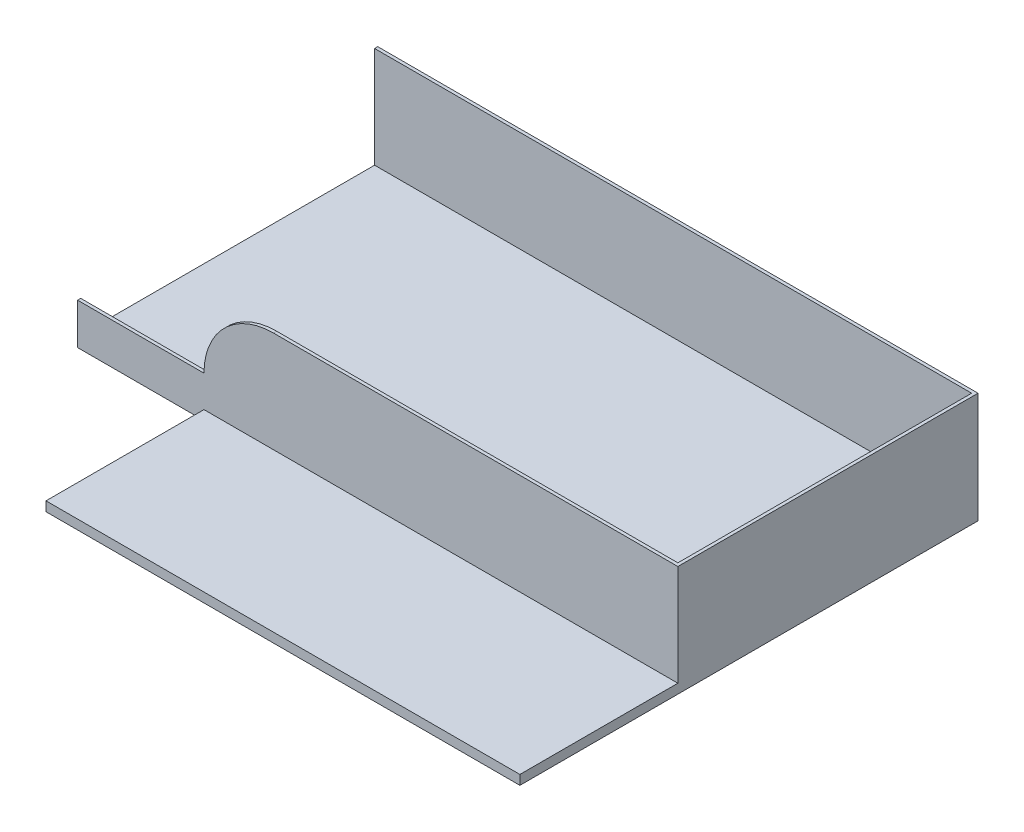
SolidWorks part; units mm, degrees
ref_plane "Front Plane" through (0, 0, 0) normal (0, 0, 1) x (1, 0, 0)
ref_plane "Top Plane" through (0, 0, 0) normal (0, 1, 0) x (1, 0, 0)
ref_plane "Right Plane" through (0, 0, 0) normal (1, 0, 0) x (0, 0, -1)
sketch "Sketch1" plane through (0, 0, 0) normal (0, 1, 0) x (1, 0, 0)
  line L0 (0, -10) -> (1890, -10)
  line L1 (0, 0) -> (1900, 0)
  line L2 (0, 0) -> (0, -950)
  line L3 (0, -950) -> (1900, -950)
  line L4 (1900, 0) -> (1900, -950)
  line L5 (1890, -10) -> (1890, -950)
  line L8 (400, -1450) -> (400, -950)
  line L9 (1900, -950) -> (0, -950)
  line L10 (1900, -950) -> (1900, -1450)
  line L11 (1900, -1450) -> (400, -1450)
  line L12 (10, -940) -> (1890, -940) construction
  line L13 (10, -10) -> (10, -940) construction
  line L14 (10, -10) -> (1890, -10) construction
  line L15 (1890, -10) -> (1890, -940) construction
  dimension "D1" = 1900
  dimension "D2" = 950
  dimension "D4" = 500
  dimension "D5" = 1500
  dimension "D3" = 10
extrude "Boss-Extrude1" add sketch "Sketch1" along normal blind 30 contours L2 L1 L4 L3
extrude "Boss-Extrude2" add sketch "Sketch1<3>" along normal blind 350 contours L4 L1 L2 L3 L0 L5 region at (21.2426, 0, 5)
sketch "Sketch1<3>" plane through (0, 0, 0) normal (0, 1, 0) x (1, 0, 0) same geometry as "Sketch1"
extrude "Boss-Extrude4" add sketch "Sketch1<4>" along normal blind 30 contours L3 L11 L10 region at (1150, 0, 1200)
sketch "Sketch1<4>" plane through (0, 0, 0) normal (0, 1, 0) x (1, 0, 0) same geometry as "Sketch1"
sketch "Sketch3" plane through (0, 0, 950) normal (0, 0, 1) x (1, 0, 0)
  line L1 (400, 30) -> (1900, 30)
  line L2 (400, 30) -> (400, 130)
  line L3 (620, 350) -> (1900, 350)
  line L4 (1900, 30) -> (1900, 350)
  line L5 (0, 30) -> (400, 30)
  line L6 (0, 30) -> (0, 130)
  line L7 (0, 130) -> (400, 130)
  line L8 (400, 30) -> (400, 130)
  arc A0 (400, 130) -> (620, 350) centre (620, 130) cw
  line M6 (400, 30) -> (0, 30)
  dimension "D1" = 220
  dimension "D2" = 100
extrude "Boss-Extrude5" add sketch "Sketch3" against normal blind 10 contours A0 L2 L1 L4 L3 | L7 L6 L2 M6 region at (1165.5013, 187.5481, 950) region at (200, 80, 950)
